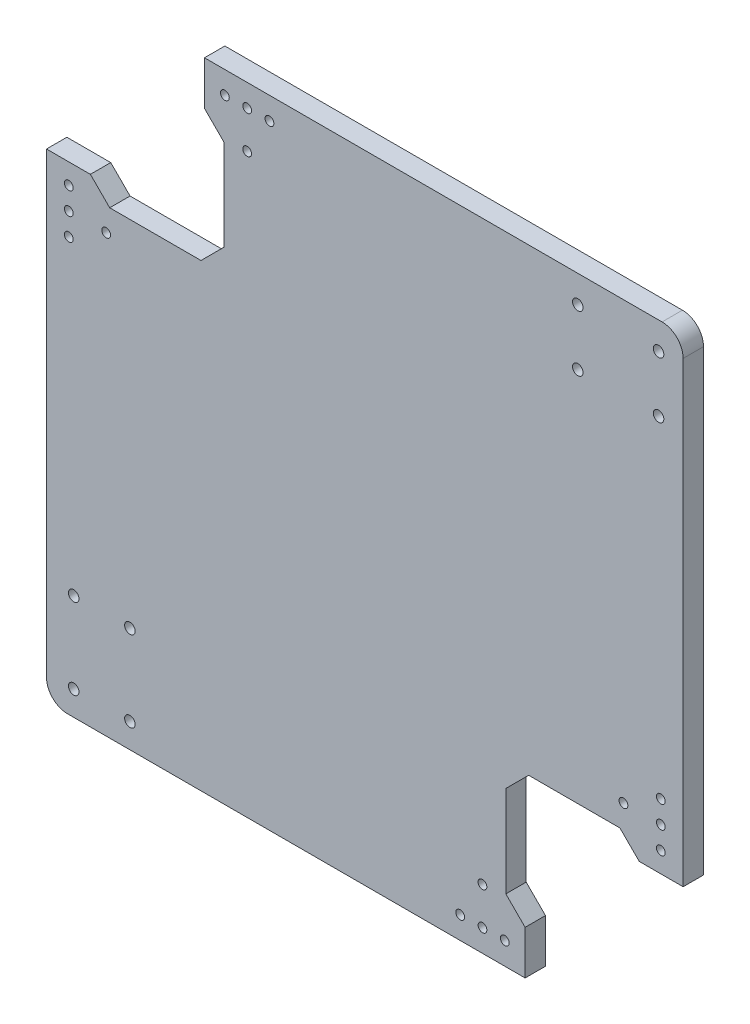
SolidWorks part; units mm, degrees
ref_plane "Front Plane" through (0, 0, 0) normal (0, 0, 1) x (1, 0, 0)
ref_plane "Top Plane" through (0, 0, 0) normal (0, 1, 0) x (1, 0, 0)
ref_plane "Right Plane" through (0, 0, 0) normal (1, 0, 0) x (0, 0, -1)
sketch "Sketch1" plane through (0, 0, 0) normal (0, 0, 1) x (1, 0, 0)
  line L0 (261.6295, 0) -> (261.6295, 101)
  line L1 (0, 0) -> (261.6295, 0)
  line L2 (0, 0) -> (0, 261.6295)
  line L3 (101, 362.6295) -> (362.6295, 362.6295)
  line L4 (362.6295, 101) -> (362.6295, 362.6295)
  line L5 (261.6295, 101) -> (362.6295, 101)
  line L6 (0, 261.6295) -> (101, 261.6295)
  line L7 (101, 261.6295) -> (101, 362.6295)
  line L8 (50.5, 312.1295) -> (312.1295, 50.5) construction
  point P12 (312.1295, 101)
  point P14 (261.6295, 50.5)
  point P16 (101, 312.1295)
  dimension "D1" = 101
  dimension "D2" = 370
extrude "Boss-Extrude1" add sketch "Sketch1" along normal blind 11.6 contours L2 L6 L7 L3 L4 L5 L0 L1
chamfer "Chamfer1" distance 13 angle 45 2 edges at (101, 261.6295, 5.8) (261.6295, 101, 5.8)
sketch "Sketch2" plane through (0, 101, 0) normal (0, -1, 0) x (1, 0, 0)
  line L0 (274.6295, 11.6) -> (362.6295, 11.6) construction
  line L1 (362.6295, 11.6) -> (337.6295, 11.6)
  line L2 (362.6295, 11.6) -> (362.6295, 0)
  line L3 (362.6295, 0) -> (337.6295, 0)
  line L4 (337.6295, 11.6) -> (337.6295, 0)
  line L5 (362.6295, 11.6) -> (362.6295, 0) construction
  line L6 (274.6295, 0) -> (362.6295, 0) construction
  dimension "D1" = 25
extrude "Boss-Extrude2" add sketch "Sketch2" along normal blind 11
ref_plane "Plane1" through (0, 0, 0) normal (0.7071, -0.7071, 0) x (-0.7071, -0.7071, 0)
ref_plane "Plane3" through (181.3148, 181.3148, 0) normal (-0.7071, -0.7071, 0) x (-0.7071, 0.7071, 0)
mirror "Mirror1" about plane through (181.3148, 181.3148, 0) normal (-0.7071, -0.7071, 0) of "Boss-Extrude2"
mirror "Mirror2" about plane through (0, 0, 0) normal (0.7071, -0.7071, 0) of "Mirror1", "Boss-Extrude2"
chamfer "Chamfer2" distance 11 angle 45 4 edges at (101, 337.6295, 5.8) (25, 261.6295, 5.8) (261.6295, 25, 5.8) (337.6295, 101, 5.8)
sketch "Sketch3" plane through (0, 0, 11.6) normal (0, 0, 1) x (1, 0, 0)
  line L1 (0, 0) -> (272.6295, 0) construction
  line L2 (176.4534, 186.1761) -> (186.1761, 176.4534) construction
  line L3 (-38.8909, -38.8909) -> (38.8909, 38.8909) construction
  line L4 (261.0295, 12.7) -> (261.0295, 101.6) construction
  line L5 (261.0295, 101.6) -> (349.9295, 101.6) construction
  circle A0 centre (261.0295, 12.7) radius 2.5
  circle A3 centre (248.3295, 12.7) radius 2.5
  circle A4 centre (235.6295, 12.7) radius 2.5
  circle A5 centre (349.9295, 101.6) radius 2.5
  circle A6 centre (349.9295, 114.3) radius 2.5
  circle A7 centre (349.9295, 127) radius 2.5
  circle A8 centre (127, 349.9295) radius 2.5
  circle A9 centre (114.3, 349.9295) radius 2.5
  circle A10 centre (101.6, 349.9295) radius 2.5
  circle A11 centre (12.7, 261.0295) radius 2.5
  circle A12 centre (12.7, 235.6295) radius 2.5
  circle A13 centre (12.7, 248.3295) radius 2.5
  dimension "D4" = 12.7
  dimension "D5" = 5
  dimension "D1" = 88.9
  dimension "D2" = 12.7
  dimension "D3" = 3
extrude "Cut-Extrude1" cut sketch "Sketch3" against normal through all
sketch "Sketch4" plane through (0, 0, 11.6) normal (0, 0, 1) x (1, 0, 0)
  line L0 (10, 37) -> (53, 37) construction
  line L1 (10, 7) -> (53, 7)
  line L2 (10, 7) -> (10, 67)
  line L3 (10, 67) -> (53, 67)
  line L4 (53, 7) -> (53, 67)
  line L5 (31.5, 7) -> (31.5, 67) construction
  line L6 (0, 0) -> (272.6295, 0) construction
  line L7 (0, 0) -> (0, 272.6295) construction
  circle A0 centre (15.5, 14) radius 3
  circle A1 centre (47.5, 14) radius 3
  circle A2 centre (47.5, 60) radius 3
  circle A3 centre (15.5, 60) radius 3
  dimension "D3" = 6
  dimension "D4" = 16
  dimension "D5" = 23
  dimension "D1" = 43
  dimension "D2" = 60
  dimension "D6" = 7
  dimension "D7" = 10
extrude "Cut-Extrude2" cut sketch "Sketch4" against normal through all contours A0 | A1 | A2 | A3 region at (15.5, 14, 11.6) region at (47.5, 14, 11.6) region at (47.5, 60, 11.6) region at (15.5, 60, 11.6)
mirror "Mirror3" about plane through (181.3148, 181.3148, 0) normal (-0.7071, -0.7071, 0) of "Cut-Extrude2"
sketch "Sketch5" plane through (0, 0, 11.6) normal (0, 0, 1) x (1, 0, 0)
  line L1 (0, 0) -> (272.6295, 0) construction
  line L2 (268.1295, 94.5) -> (350.7958, 11.8337) construction
  line L3 (261.6295, 88) -> (274.6295, 101) construction
  line L4 (0, 0) -> (362.6295, 362.6295) construction
  circle A0 centre (248.3295, 34) radius 2.5
  circle A1 centre (235.6295, 12.7) radius 2.5 construction
  circle A2 centre (328.6295, 114.3) radius 2.5
  circle A3 centre (114.3, 328.6295) radius 2.5
  circle A4 centre (34, 248.3295) radius 2.5
  point P6 (248.3295, 12.7)
  point P14 (349.9295, 114.3)
  dimension "D1" = 34
extrude "Cut-Extrude3" cut sketch "Sketch5" against normal blind 15
fillet "Fillet1" radius 12 2 edges at (362.6295, 362.6295, 5.8) (0, 0, 5.8)
